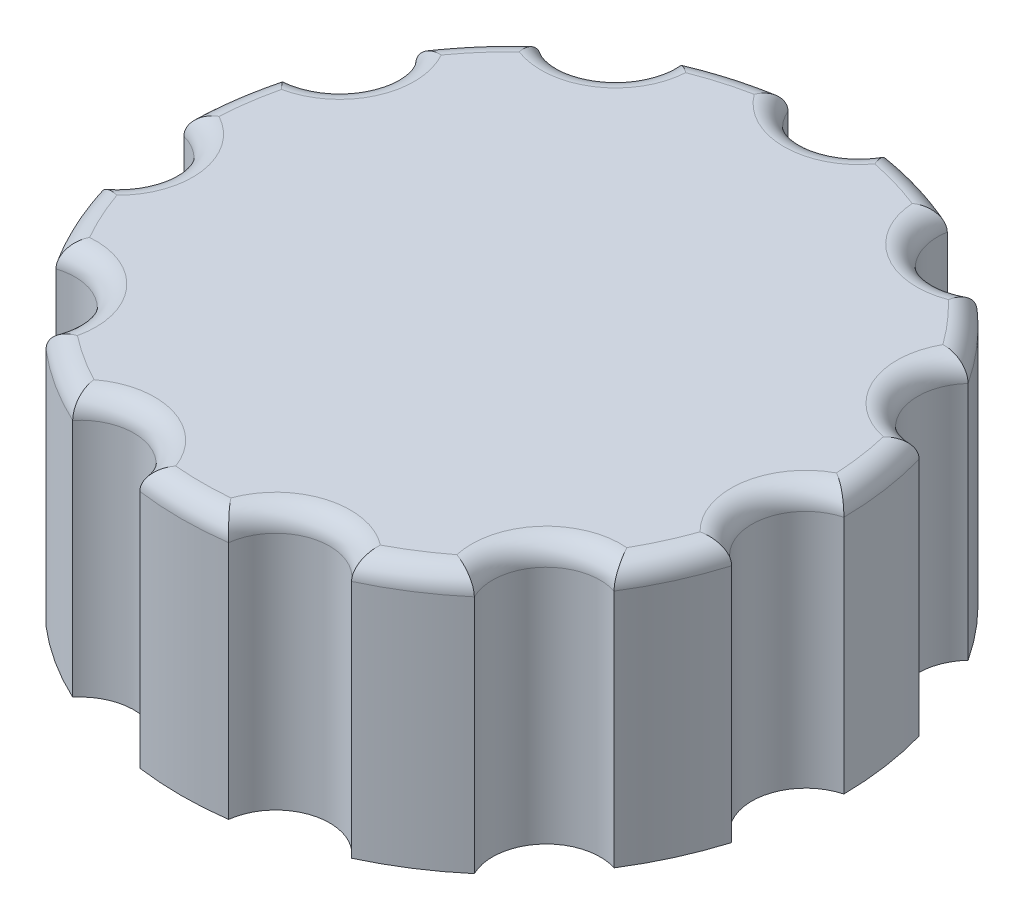
SolidWorks part; units mm, degrees
ref_plane "Front Plane" through (0, 0, 0) normal (0, 0, 1) x (1, 0, 0)
ref_plane "Top Plane" through (0, 0, 0) normal (0, 1, 0) x (1, 0, 0)
ref_plane "Right Plane" through (0, 0, 0) normal (1, 0, 0) x (0, 0, -1)
sketch "Sketch1" plane through (0, 0, 0) normal (0, 1, 0) x (1, 0, 0)
  line L0 (0, 9.5) -> (0, 10) construction
  circle A0 centre (0, 0) radius 2.85
  circle A1 centre (0, 0) radius 9.5
  circle A2 centre (0, 10) radius 1.55
  circle A3 centre (5.4064, 8.4125) radius 1.55
  circle A4 centre (9.0963, 4.1542) radius 1.55
  circle A5 centre (9.8982, -1.4231) radius 1.55
  circle A6 centre (7.5575, -6.5486) radius 1.55
  circle A7 centre (2.8173, -9.5949) radius 1.55
  circle A8 centre (-2.8173, -9.5949) radius 1.55
  circle A9 centre (-7.5575, -6.5486) radius 1.55
  circle A10 centre (-9.8982, -1.4231) radius 1.55
  circle A11 centre (-9.0963, 4.1542) radius 1.55
  circle A12 centre (-5.4064, 8.4125) radius 1.55
  point P31 (0, 0)
  dimension "D1" = 5.7
  dimension "D2" = 19
  dimension "D3" = 3.1
  dimension "D4" = 0.5
  dimension "D5" = 11
extrude "Boss-Extrude1" add sketch "Sketch1" against normal blind 6.5 contours A1 A12 A11 A10 A9 A8 A7 A6 A5 A4 A3 A2 A0 region at (8.0988, 0, 1.1644)
extrude "Boss-Extrude2" add sketch "Sketch1<2>" along normal blind 1 contours A1 A12 A11 A10 A9 A8 A7 A6 A5 A4 A3 A2 A0 | A0 region at (0, 0, 0) region at (8.0988, 0, 1.1644)
sketch "Sketch1<2>" plane through (0, 0, 0) normal (0, 1, 0) x (1, 0, 0) same geometry as "Sketch1"
fillet "Fillet1" radius 0.6 22 edges at (-2.6765, 1, -9.1152) (0, 1, -8.45) (2.6765, 1, -9.1152) (4.5684, 1, -7.1086) (7.1796, 1, -6.2212) (7.6864, 1, -3.5103) (9.4033, 1, -1.352) (8.364, 1, 1.2026) (8.6415, 1, 3.9464) (6.3861, 1, 5.5336) (5.1361, 1, 7.9919) (2.3806, 1, 8.1077) (0, 1, 9.5) (-2.3806, 1, 8.1077) (-5.1361, 1, 7.9919) (-6.3861, 1, 5.5336) (-8.6415, 1, 3.9464) (-8.364, 1, 1.2026) (-9.4033, 1, -1.352) (-7.6864, 1, -3.5103) (-7.1796, 1, -6.2212) (-4.5684, 1, -7.1086)
